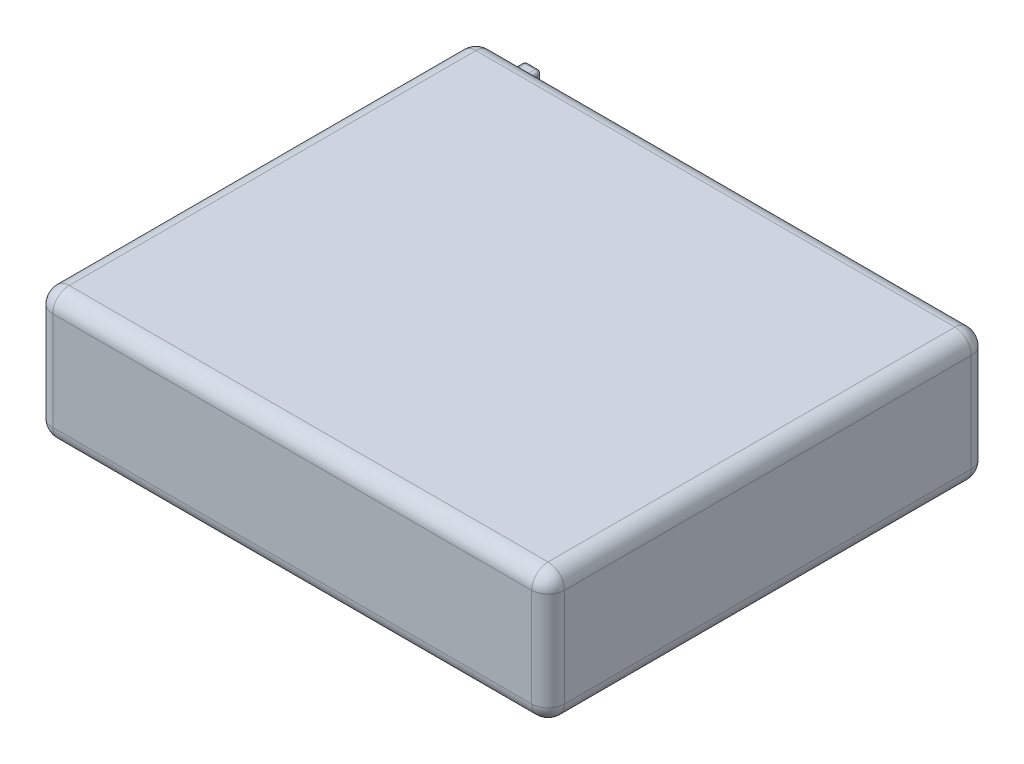
SolidWorks part; units mm, degrees
ref_plane "Front Plane" through (0, 0, 0) normal (0, 0, 1) x (1, 0, 0)
ref_plane "Top Plane" through (0, 0, 0) normal (0, 1, 0) x (1, 0, 0)
ref_plane "Right Plane" through (0, 0, 0) normal (1, 0, 0) x (0, 0, -1)
sketch "Sketch1" plane through (0, 0, 0) normal (0, 1, 0) x (1, 0, 0)
  line L1 (-39, 33.5) -> (39, 33.5)
  line L2 (-39, 33.5) -> (-39, -33.5)
  line L3 (-39, -33.5) -> (39, -33.5)
  line L4 (39, 33.5) -> (39, -33.5)
  line L5 (-39, 33.5) -> (39, -33.5) construction
  line L6 (-39, -33.5) -> (39, 33.5) construction
  point P0 (0, 0)
  dimension "D1" = 78
  dimension "D2" = 67
extrude "Boss-Extrude1" add sketch "Sketch1" along normal blind 10 and the other way blind 10
fillet "Fillet1" radius 2.5 12 edges at (-39, -10, 0) (0, -10, -33.5) (-39, 0, -33.5) (39, -10, 0) (39, 0, -33.5) (0, -10, 33.5) (-39, 0, 33.5) (39, 0, 33.5) (0, 10, 33.5) (-39, 10, 0) (0, 10, -33.5) (39, 10, 0)
sketch "Sketch2" plane through (0, 0, -33.5) normal (0, 0, -1) x (-1, 0, 0)
  line L1 (36.5, -7.5) -> (36.5, 7.5) construction
  line L2 (34, 5) -> (36.5, 5)
  line L3 (34, 5) -> (34, -5)
  line L4 (34, -5) -> (36.5, -5)
  line L5 (36.5, 5) -> (36.5, -5)
  line L6 (36.5, 7.5) -> (-36.5, 7.5) construction
  line L7 (-36.5, -7.5) -> (36.5, -7.5) construction
  dimension "D1" = 2.5
  dimension "D2" = 2.5
  dimension "D3" = 2.5
extrude "Boss-Extrude2" add sketch "Sketch2" along normal blind 5
fillet "Fillet2" radius 0.5 12 edges at (-34, 0, -33.5) (-34, -5, -36) (-35.25, -5, -33.5) (-35.25, -5, -38.5) (-34, 0, -38.5) (-35.25, 5, -38.5) (-34, 5, -36) (-35.25, 5, -33.5) (-36.5, -5, -36) (-36.5, 0, -38.5) (-36.5, 5, -36) (-36.5, 0, -33.5)
